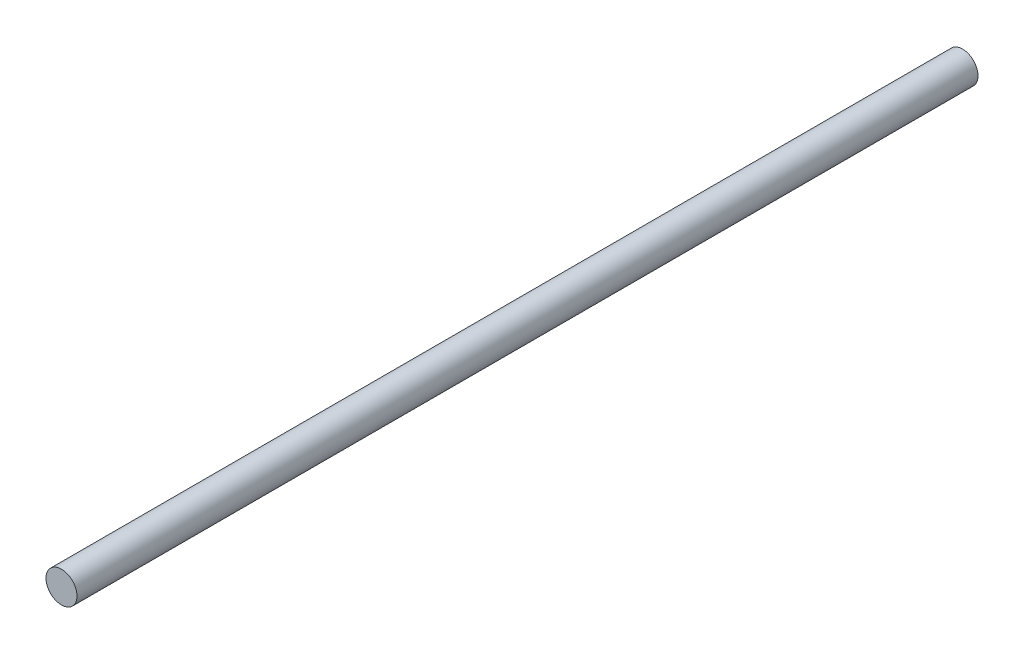
SolidWorks part; units mm, degrees
material "AISI 316 Stainless Steel Sheet (SS)"
ref_plane "Front (1)" through (0, 0, 0) normal (0, 0, 1) x (1, 0, 0)
ref_plane "Top (2)" through (0, 0, 0) normal (0, 1, 0) x (1, 0, 0)
ref_plane "Right (3)" through (0, 0, 0) normal (1, 0, 0) x (0, 0, -1)
ref_axis "X Axis" through (13.5064, 0, 0) along (-1, 0, 0)
ref_axis "Y Axis" through (0, 12.3593, 0) along (0, -1, 0)
ref_axis "Z Axis" through (0, 0, 14.1119) along (0, 0, -1)
sketch "Sketch2" plane through (0, 0, 0) normal (1, 0, 0) x (0, 0, -1)
  line L0 (0, 0) -> (-4, 0) construction
  line L1 (0, 0) -> (232.3477, 0)
  line L2 (0, 0) -> (0, 4)
  line L3 (0, 4) -> (232.3477, 4)
  line L4 (232.3477, 0) -> (232.3477, 4)
  dimension "D1" = 8
  dimension "D2" = 232.3477
revolve "Revolve1" add sketch "Sketch2" angle 360 about L0
cosmetic thread "Cosmetic Thread2" parameters "D2"=6.891
